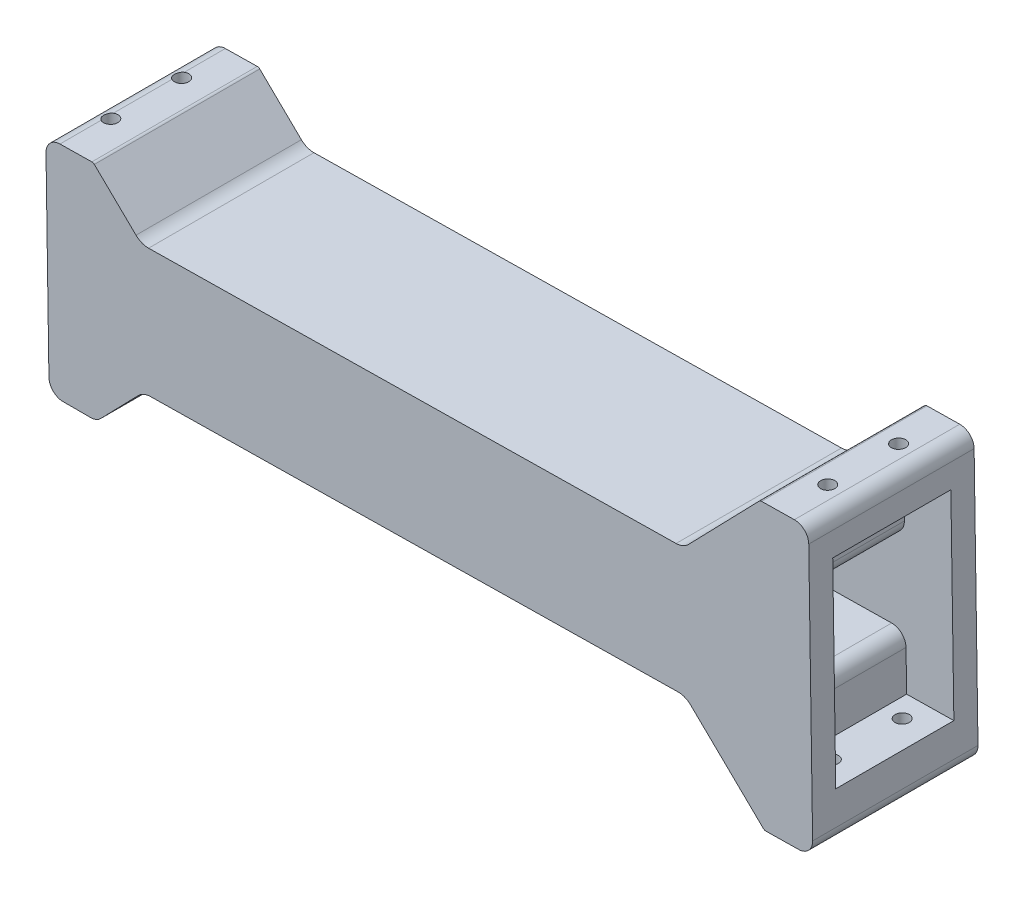
SolidWorks part; units mm, degrees
ref_plane "前视基准面" through (0, 0, 0) normal (0, 0, 1) x (1, 0, 0)
ref_plane "上视基准面" through (0, 0, 0) normal (0, 1, 0) x (1, 0, 0)
ref_plane "右视基准面" through (0, 0, 0) normal (1, 0, 0) x (0, 0, -1)
other "Configuration Table"
sketch "草图1" plane through (0, 0, 0) normal (0, 0, 1) x (1, 0, 0)
  line L1 (98.2137, 7.7668) -> (98.9244, -39.0798)
  line L24 (250.6594, -46.4269) -> (297.3235, -45.7189)
  line L25 (297.3235, -45.7189) -> (297.278, -42.7193)
  line L26 (297.278, -42.7193) -> (250.6139, -43.4272)
  line L27 (250.0898, -43.2194) -> (234.6713, -28.2617)
  line L28 (232.5824, -30.415) -> (248.0009, -45.3727)
  line L29 (249.7037, 16.5659) -> (296.3678, 17.2738)
  line L30 (296.3678, 17.2738) -> (296.3223, 20.2735)
  line L31 (296.3223, 20.2735) -> (249.6582, 19.5655)
  line L32 (247.0329, 18.4312) -> (232.0753, 3.0126)
  line L33 (234.2285, 0.9238) -> (249.1862, 16.3423)
  line L34 (120.4241, -31.9008) -> (232.0584, -30.2072)
  line L35 (232.0129, -27.2075) -> (120.3786, -28.9012)
  line L36 (108.6788, -39.0798) -> (96.3187, -39.0798)
  line L37 (96.3187, -39.0798) -> (96.3187, -42.2677)
  line L38 (96.3187, -42.2677) -> (108.7243, -42.0795)
  line L39 (107.9203, 10.9144) -> (95.5616, 10.7269)
  line L40 (95.5616, 10.7269) -> (95.6071, 7.7273)
  line L41 (95.6071, 7.7273) -> (107.9658, 7.9148)
  line L42 (111.3495, -40.9451) -> (119.9066, -32.1245)
  line L43 (117.7533, -30.0356) -> (109.1963, -38.8562)
  line L44 (119.969, -1.9043) -> (231.6033, -0.2106)
  line L45 (231.5578, 2.789) -> (119.9235, 1.0954)
  line L46 (108.4899, 7.7069) -> (117.3105, -0.8501)
  line L47 (119.3994, 1.3032) -> (110.5788, 9.8602)
  line L49 (259.6417, 16.7167) -> (260.5973, -46.2761)
  arc A16 (250.0898, -43.2194) -> (250.6139, -43.4272) centre (250.6027, -42.6907) ccw
  arc A17 (248.0009, -45.3727) -> (250.6594, -46.4269) centre (250.6027, -42.6907) ccw
  arc A18 (234.6713, -28.2617) -> (232.0129, -27.2075) centre (232.0695, -30.9437) ccw
  arc A19 (232.5824, -30.415) -> (232.0584, -30.2072) centre (232.0695, -30.9437) ccw
  arc A20 (249.6582, 19.5655) -> (247.0329, 18.4312) centre (249.7149, 15.8294) ccw
  arc A21 (249.7037, 16.5659) -> (249.1862, 16.3423) centre (249.7149, 15.8294) ccw
  arc A22 (231.5578, 2.789) -> (232.0753, 3.0126) centre (231.5466, 3.5255) ccw
  arc A23 (231.6033, -0.2106) -> (234.2285, 0.9238) centre (231.5466, 3.5255) ccw
  arc A24 (120.3786, -28.9012) -> (117.7533, -30.0356) centre (120.4352, -32.6373) ccw
  arc A25 (120.4241, -31.9008) -> (119.9066, -32.1245) centre (120.4352, -32.6373) ccw
  arc A26 (108.6788, -39.0798) -> (109.1963, -38.8562) centre (108.6676, -38.3433) ccw
  arc A27 (108.7243, -42.0795) -> (111.3495, -40.9451) centre (108.6676, -38.3433) ccw
  arc A28 (110.5788, 9.8602) -> (107.9203, 10.9144) centre (107.977, 7.1782) ccw
  arc A29 (108.4899, 7.7069) -> (107.9658, 7.9148) centre (107.977, 7.1782) ccw
  arc A30 (119.3994, 1.3032) -> (119.9235, 1.0954) centre (119.9123, 1.8319) ccw
  arc A31 (117.3105, -0.8501) -> (119.969, -1.9043) centre (119.9123, 1.8319) ccw
extrude "凸台-拉伸1" add sketch "草图1" against normal blind 35 contours A31 L46 A29 L41 L1 L36 A26 L43 A24 L35 A18 L27 A16 L26 L49 L29 A21 L33 A23 L44 region at (183.3823, -14.4406, 0)
sketch "草图2" plane through (259.8355, 3.9421, 0) normal (0.9999, 0.0152, 0) x (0, 0, -1)
  line L0 (35, -3.724) -> (0, -3.724) construction
  line L1 (35, -3.724) -> (0, -3.724) construction
  line L2 (35, -30.724) -> (0, -30.724) construction
  line L3 (35, -30.724) -> (0, -30.724) construction
  line L4 (0, -30.724) -> (35, -3.724) construction
  line L5 (35, -30.724) -> (0, -3.724) construction
  line L6 (35, 12.776) -> (35, -47.224) construction
  line L7 (5, -25.724) -> (30, -25.724)
  line L8 (5, -25.724) -> (5, -8.724)
  line L9 (5, -8.724) -> (30, -8.724)
  line L10 (30, -25.724) -> (30, -8.724)
  line L11 (5, -25.724) -> (30, -8.724) construction
  line L12 (5, -8.724) -> (30, -25.724) construction
  point P4 (17.5, -17.224)
  dimension "D1" = 5
  dimension "D2" = 5
extrude "切除-拉伸1" cut sketch "草图2" against normal through all
sketch "草图4" plane through (259.8355, 3.9421, 0) normal (0.9999, 0.0152, 0) x (0, 0, -1)
  line L4 (0, 12.776) -> (0, -47.224)
  line L5 (0, -47.224) -> (35, -47.224)
  line L6 (35, -47.224) -> (35, 12.776)
  line L7 (35, 12.776) -> (0, 12.776)
  line L8 (0, 12.776) -> (0, -47.224)
  line L9 (0, -47.224) -> (35, -47.224)
  line L10 (35, -47.224) -> (35, 12.776)
  line L11 (35, 12.776) -> (0, 12.776)
  line L12 (5, 4.776) -> (30, 4.776)
  line L13 (5, -37.224) -> (30, -37.224)
  line L16 (5, 7.776) -> (5, -42.224)
  line L17 (5, -42.224) -> (30, -42.224)
  line L18 (30, -42.224) -> (30, 7.776)
  line L19 (30, 7.776) -> (5, 7.776)
  line L20 (5, 7.776) -> (5, -42.224)
  line L21 (5, -42.224) -> (30, -42.224)
  line L22 (30, -42.224) -> (30, 7.776)
  line L23 (30, 7.776) -> (5, 7.776)
  line M9 (5, -8.724) -> (30, -8.724)
  line M11 (30, -25.724) -> (5, -25.724)
  dimension "D3" = 3
  dimension "D4" = 5
  dimension "D1" = 0
  dimension "D2" = 5
extrude "切除-拉伸2" cut sketch "草图4" against normal blind 10 contours L22 L23 L20 M9 | L21 L22 L20 M11 region at (259.8654, 1.9683, -17.5) region at (260.3129, -27.5283, -17.5)
ref_plane "基准面1" through (131.2411, -127.3184, 0) normal (-0.7178, 0.6963, 0) x (0, 0, 1)
sketch "草图7" plane through (98.3089, 1.4915, 0) normal (-0.9999, -0.0152, 0) x (0, 0, 1)
  line L0 (-5, 1.276) -> (-30, 1.276)
  line L1 (-30, 1.276) -> (-30, -35.576)
  line L2 (-30, -35.576) -> (-5, -35.576)
  line L3 (-5, -35.576) -> (-5, 1.276)
  line L4 (0, -40.576) -> (0, 6.276)
  line L5 (0, 6.276) -> (-35, 6.276)
  line L6 (-35, 6.276) -> (-35, -40.576)
  line L7 (-35, -40.576) -> (0, -40.576)
  line L8 (0, -40.576) -> (0, 6.276)
  line L9 (0, 6.276) -> (-35, 6.276)
  line L10 (-35, 6.276) -> (-35, -40.576)
  line L11 (-35, -40.576) -> (0, -40.576)
  line L12 (-30, -1.724) -> (-5, -1.724)
  line L13 (-30, -32.576) -> (-5, -32.576)
  line M6 (-30, -8.724) -> (-5, -8.724)
  line M8 (-5, -25.724) -> (-30, -25.724)
  dimension "D3" = 3
  dimension "D4" = 3
  dimension "D1" = 0
  dimension "D2" = 5
extrude "切除-拉伸5" cut sketch "草图7" against normal blind 10 contours L3 L0 L1 M6 | L1 L13 L3 M8 region at (98.3881, -3.7319, -17.5) region at (98.7511, -27.6551, -17.5)
fillet "圆角1" radius 3 9 edges at (250.2268, -21.9306, -17.5) (249.9689, -4.9326, -17.5) (98.9244, -39.0798, -17.5) (108.6788, -39.0798, -17.5) (260.5518, -43.2764, -17.5) (259.6417, 16.7167, -17.5) (98.2137, 7.7668, -17.5) (108.4401, -7.0798, -17.5) (108.698, -24.0778, -17.5)
sketch "草图9" plane through (0.7164, -47.2185, 0) normal (0.0152, -0.9999, 0) x (0.9999, 0.0152, 0)
  circle A2 centre (253.9263, -25) radius 1.5 construction
  circle A3 centre (253.9263, -10) radius 1.5 construction
  circle A6 centre (253.9263, -25) radius 1.5
  circle A7 centre (253.9263, -10) radius 1.5
  circle A8 centre (102.0734, -10) radius 1.5 construction
  circle A9 centre (102.0734, -25) radius 1.5 construction
  circle A10 centre (102.0734, -10) radius 1.5
  circle A11 centre (102.0734, -25) radius 1.5
extrude "切除-拉伸6" cut sketch "草图9" against normal through all
sketch "草图11" plane through (0, 0, -35) normal (0, 0, -1) x (-1, 0, 0)
  line L0 (-98.3351, -0.2323) -> (-98.8031, -31.0808) construction
  line L1 (-108.3339, -0.0806) -> (-98.3351, -0.2323) construction
  line L2 (-108.8019, -30.9291) -> (-98.8031, -31.0808) construction
  line L3 (-98.3351, -0.2323) -> (-98.8031, -31.0808)
  line L4 (-108.3339, -0.0806) -> (-98.3351, -0.2323)
  line L5 (-108.8019, -30.9291) -> (-98.8031, -31.0808)
  line L6 (-108.3339, -0.0806) -> (-108.8019, -30.9291)
extrude "切除-拉伸8" cut sketch "草图11" against normal blind 10
fillet "圆角3" radius 3 2 edges at (103.8025, -31.0049, -35) (103.3345, -0.1564, -35)
